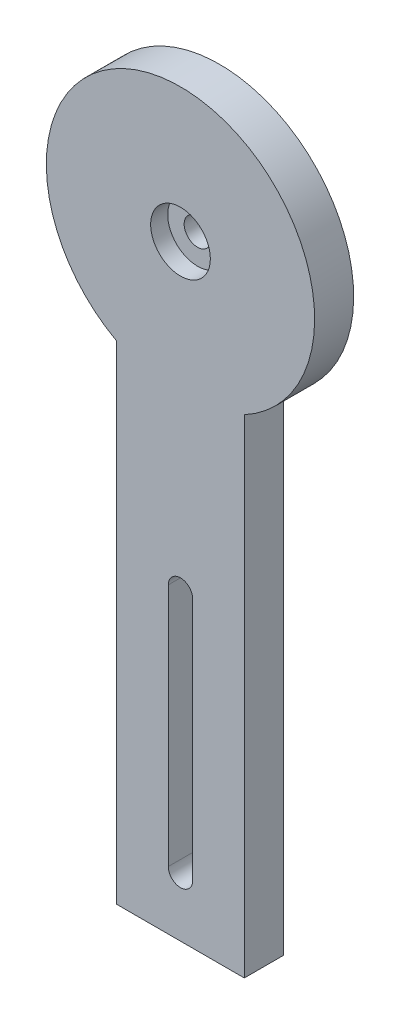
SolidWorks part; units mm, degrees
ref_plane "Piano frontale" through (0, 0, 0) normal (0, 0, 1) x (1, 0, 0)
ref_plane "Piano superiore" through (0, 0, 0) normal (0, 1, 0) x (1, 0, 0)
ref_plane "Piano destro" through (0, 0, 0) normal (1, 0, 0) x (0, 0, -1)
sketch "Schizzo1" plane through (0, 0, 0) normal (0, 0, 1) x (1, 0, 0)
  line L0 (0, 0) -> (0, 100)
  line L1 (0, 0) -> (26.16, 0)
  line L2 (26.16, 0) -> (26.16, 100)
  line L6 (0, 50) -> (13.08, 50) construction
  arc A1 (26.16, 100) -> (0, 100) centre (13.08, 124.1902) ccw
  dimension "D1" = 100
  dimension "D3" = 55
  dimension "D2" = 100
  dimension "D4" = 26.16
extrude "Estrusione-Estrusione1" add sketch "Schizzo1" along normal mid plane 8
sketch "Schizzo2" plane through (0, 0, 4) normal (0, 0, 1) x (1, 0, 0)
  line L0 (0, 50) -> (26.16, 50) construction
  line L1 (0, 100) -> (0, 0) construction
  line L2 (26.16, 0) -> (26.16, 100) construction
  line L3 (13.08, 0) -> (13.08, 99.1276) construction
  line L7 (0, 0) -> (26.16, 0) construction
  line L8 (13.08, 12) -> (13.08, 62) construction
  line L9 (10.58, 12) -> (10.58, 62)
  line L10 (15.58, 12) -> (15.58, 62)
  arc A3 (10.58, 12) -> (15.58, 12) centre (13.08, 12) ccw
  arc A4 (15.58, 62) -> (10.58, 62) centre (13.08, 62) ccw
  point P12 (13.08, 37)
  dimension "D1" = 2.5
  dimension "D3" = 62
  dimension "D2" = 12
extrude "Taglio-Estrusione1" cut sketch "Schizzo2" against normal through all
sketch "Schizzo11" plane through (0, 0, 4) normal (0, 0, 1) x (1, 0, 0)
  arc A0 (26.16, 100) -> (0, 100) centre (13.08, 124.1902) ccw construction
  arc A1 (26.16, 100) -> (0, 100) centre (13.08, 124.1902) ccw construction
hole_wizard "Foro lamato per Bullone M5 a testa esagonale-1" positions "Schizzo12" profile "Schizzo13" counterbore size "M5" standard "ISO" end condition through all
sketch "Schizzo12" plane through (0, 0, 4) normal (0, 0, 1) x (1, 0, 0)
  point P0 (13.08, 124.1902)
sketch "Schizzo13" plane through (13.08, 124.1902, 4) normal (1, 0, 0) x (0, -1, 0)
  line L0 (0, 0) -> (0, 8)
  line L1 (0, 8) -> (2.75, 8)
  line L3 (2.75, 8) -> (2.75, 3.5)
  line L4 (2.75, 3.5) -> (6.119, 3.5)
  line L5 (6.119, 3.5) -> (6.119, 0)
  line L7 (6.119, 0) -> (0, 0)
  line L11 (0, -6.35) -> (0, 107.95) construction
  dimension "Thru Hole Dia." = 5.5
  dimension "Thru Hole Depth" = 8
  dimension "C'Bore Dia." = 12.238
  dimension "C'Bore Depth" = 3.5
sketch "Schizzo15" plane through (0, 0, -4) normal (0, 0, -1) x (-1, 0, 0)
  line L0 (-10.58, 37) -> (-26.16, 37) construction
  line L1 (-10.58, 62) -> (-10.58, 12) construction
  line L2 (-26.16, 0) -> (-26.16, 100) construction
  line L3 (-26.16, 37) -> (-13.08, 0) construction
  line L4 (0, 0) -> (-26.16, 0) construction
  line L5 (-13.08, 0) -> (-13.08, 37) construction
